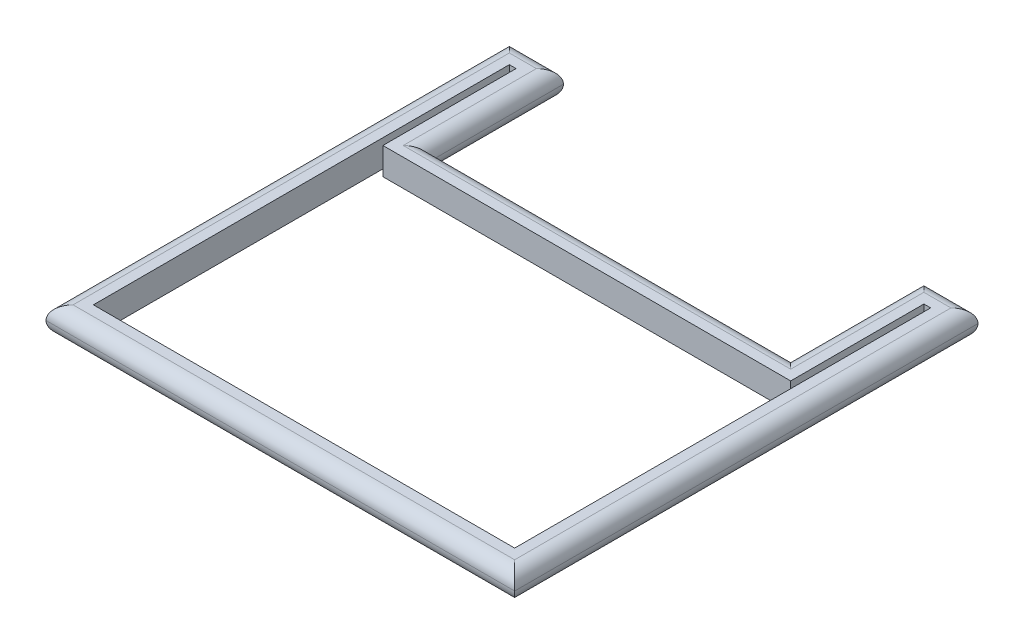
SolidWorks part; units mm, degrees
ref_plane "Front Plane" through (0, 0, 0) normal (0, 0, 1) x (1, 0, 0)
ref_plane "Top Plane" through (0, 0, 0) normal (0, 1, 0) x (1, 0, 0)
ref_plane "Right Plane" through (0, 0, 0) normal (1, 0, 0) x (0, 0, -1)
sketch "Sketch2" plane through (0, 0, 0) normal (0, 1, 0) x (1, 0, 0)
  line L0 (-147.5, 0) -> (147.5, 0) construction
  line L5 (-191.35, 195.2) -> (191.35, 195.2) construction
  line L6 (-197.7, -132.7) -> (197.7, -132.7)
  line L13 (110, 120) -> (185, 120)
  line L14 (110, 120) -> (110, -120)
  line L15 (110, -120) -> (185, -120)
  line L16 (185, 120) -> (185, -120)
  line L17 (110, 120) -> (185, -120) construction
  line L18 (110, -120) -> (185, 120) construction
  line L19 (-185, 120) -> (-110, 120)
  line L20 (-185, 120) -> (-185, -120)
  line L21 (-185, -120) -> (-110, -120)
  line L22 (-110, 120) -> (-110, -120)
  line L23 (-185, 120) -> (-110, -120) construction
  line L24 (-185, -120) -> (-110, 120) construction
  line L26 (-110, -37.5) -> (110, -37.5)
  line L27 (-110, -37.5) -> (-110, 37.5)
  line L28 (-110, 37.5) -> (110, 37.5)
  line L29 (110, -37.5) -> (110, 37.5)
  line L30 (-110, -37.5) -> (110, 37.5) construction
  line L31 (-110, 37.5) -> (110, -37.5) construction
  line L41 (-197.7, -132.7) -> (-197.7, 132.7)
  line L42 (-191.35, 132.7) -> (191.35, 132.7) construction
  line L43 (197.7, -132.7) -> (197.7, 132.7)
  line L44 (-197.7, -132.7) -> (197.7, 132.7) construction
  line L45 (-197.7, 132.7) -> (197.7, -132.7) construction
  line L47 (-197.7, 132.7) -> (-197.7, 257.7)
  line L48 (-197.7, 257.7) -> (-191.35, 257.7)
  line L49 (-191.35, 132.7) -> (-191.35, 257.7)
  line L51 (191.35, 132.7) -> (191.35, 257.7)
  line L52 (191.35, 257.7) -> (197.7, 257.7)
  line L53 (197.7, 132.7) -> (197.7, 257.7)
  line L54 (-191.35, 132.7) -> (191.35, 132.7)
  line L55 (219.925, 132.7) -> (219.925, 279.925)
  line L56 (169.125, 279.925) -> (219.925, 279.925)
  line L57 (169.125, 154.925) -> (169.125, 279.925)
  line L58 (-169.125, 154.925) -> (169.125, 154.925)
  line L59 (-169.125, 154.925) -> (-169.125, 279.925)
  line L60 (-219.925, 279.925) -> (-169.125, 279.925)
  line L61 (-219.925, 132.7) -> (-219.925, 279.925)
  line L62 (-219.925, -154.925) -> (-219.925, 132.7)
  line L63 (-219.925, -154.925) -> (219.925, -154.925)
  line L64 (219.925, -154.925) -> (219.925, 132.7)
  circle A0 centre (0, 304.925) radius 150
  point P2 (0, 0)
  point P13 (147.5, 0)
  point P18 (-147.5, 0)
  point P23 (0, 0)
  point P24 (0, 0)
  point P35 (0, 195.2)
  dimension "D1" = 300
  dimension "D2" = 75
  dimension "D3" = 240
  dimension "D4" = 75
  dimension "D5" = 220
  dimension "D6" = 12.7
  dimension "D7" = 12.7
  dimension "D8" = 6.35
  dimension "D9" = 125
  dimension "D10" = 22.225
extrude "Boss-Extrude1" add sketch "Sketch2" along normal blind 25.4 contours L63 L64 L55 L56 L57 L58 L59 L60 L61 L62 L49 L54 L51 L52 L53 L43 L6 L41 L47 L48 region at (213.7398, 0, 11.1125)
fillet "Fillet1" radius 12.7 16 edges at (0, 0, 154.925) (0, 25.4, 154.925) (-219.925, 0, -62.5) (-194.525, 0, -279.925) (-219.925, 25.4, -62.5) (-194.525, 25.4, -279.925) (-169.125, 0, -217.425) (-169.125, 25.4, -217.425) (0, 0, -154.925) (0, 25.4, -154.925) (219.925, 0, -62.5) (219.925, 25.4, -62.5) (194.525, 0, -279.925) (194.525, 25.4, -279.925) (169.125, 0, -217.425) (169.125, 25.4, -217.425)
